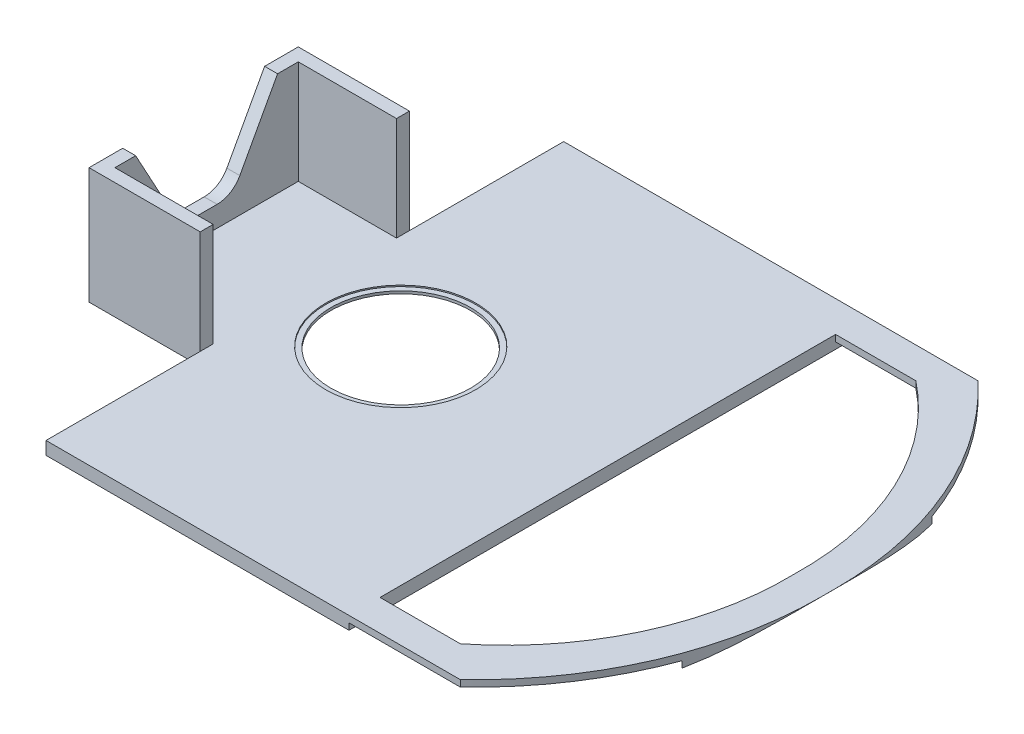
SolidWorks part; units mm, degrees
ref_plane "Front Plane" through (0, 0, 0) normal (0, 0, 1) x (1, 0, 0)
ref_plane "Top Plane" through (0, 0, 0) normal (0, 1, 0) x (1, 0, 0)
ref_plane "Right Plane" through (0, 0, 0) normal (1, 0, 0) x (0, 0, -1)
sketch "Sketch1" plane through (0, 0, 0) normal (0, 1, 0) x (1, 0, 0)
  line L0 (0, 0) -> (203.0139, 0)
  line L1 (0, 100) -> (245, 100) construction
  line L2 (0, 200) -> (0, 0)
  line L3 (191.0139, 12) -> (160, 12)
  line L4 (160, 12) -> (160, 188)
  line L5 (191.0139, 188) -> (160, 188)
  line L6 (0, 200) -> (203.0139, 200)
  line L7 (245, 0) -> (245, 209.5631) construction
  line L8 (245, 100) -> (232.199, 100)
  arc A0 (245, 100) -> (203.0139, 0) centre (111.4511, 97.2578) cw
  arc A1 (232.199, 100) -> (191.0139, 12) centre (123.4511, 97.2578) cw
  arc A2 (245, 100) -> (203.0139, 200) centre (111.4511, 102.7422) ccw
  arc A3 (232.199, 100) -> (191.0139, 188) centre (123.4511, 102.7422) ccw
  point P13 (160, 100)
  dimension "D5" = 12
  dimension "D6" = 12
  dimension "D1" = 200
  dimension "D2" = 12
  dimension "D3" = 160
  dimension "D4" = 245
extrude "Boss-Extrude1" add sketch "Sketch1" along normal blind 5 contours A3 A2 L6 L2 L0 A0 A1 L3 L4 L5 region at (94.4936, 0, -100)
sketch "Sketch6" plane through (0, 5, 0) normal (0, 1, 0) x (1, 0, 0)
  line L0 (0, 100) -> (160, 100) construction
  line L1 (0, 200) -> (0, 0) construction
  line L2 (160, 12) -> (160, 188) construction
  line L3 (42.952, 200) -> (42.952, 140.4135)
  line L4 (0, 0) -> (42.952, 0)
  line L5 (0, 0) -> (0, 59.5865)
  line L6 (0, 59.5865) -> (42.952, 59.5865)
  line L7 (42.952, 0) -> (42.952, 59.5865)
  line L8 (0, 140.4135) -> (42.952, 140.4135)
  line L9 (0, 200) -> (0, 140.4135)
  line L10 (0, 200) -> (42.952, 200)
  circle A0 centre (80, 100) radius 27
  dimension "D1" = 54
extrude "Cut-Extrude4" cut sketch "Sketch6" against normal through all contours A0
sketch "Sketch4" plane through (0, 0, 0) normal (0, 0, 1) x (1, 0, 0)
  line L0 (203.0139, 0) -> (245.0282, 0) construction
  line L1 (160, 2.5) -> (237.0282, 2.5)
  line L2 (160, 2.5) -> (160, 0)
  line L3 (160, 0) -> (237.0282, 0)
  line L4 (237.0282, 2.5) -> (237.0282, 0)
  line L6 (237.0282, 0) -> (245.0282, 0)
  line L7 (245.0282, 0) -> (245.0282, 5)
  arc A0 (237.0282, 0) -> (245.0282, 5) centre (228.901, 21.9035) ccw
  line M1 (0, 0) -> (203.0139, 0)
  line M2 (203.0139, 0) -> (203.0139, 5)
  dimension "D1" = 2.5
  dimension "D2" = 5
  dimension "D3" = 8
extrude "Cut-Extrude2" cut sketch "Sketch4" against normal through all contours L1 L2 M1 M2 | L4 L1 L3 M2 | A0 L6 L7 region at (242.5815, 1.5469, 0) region at (181.507, 1.25, 0) region at (220.021, 1.25, 0)
sketch "Sketch7" plane through (0, 5, 0) normal (0, 1, 0) x (1, 0, 0)
  circle A0 centre (80, 100) radius 29
  dimension "D1" = 58
extrude "Cut-Extrude5" cut sketch "Sketch7" against normal blind 0.5
extrude "Cut-Extrude6" cut sketch "Sketch6<4>" against normal through all
sketch "Sketch6<4>" plane through (0, 5, 0) normal (0, 1, 0) x (1, 0, 0) same geometry as "Sketch6"
sketch "Sketch8" plane through (0, 0, 0) normal (0, -1, 0) x (1, 0, 0)
  line L0 (0, -100) -> (160, -100) construction
  line L1 (0, -140.4135) -> (0, -59.5865) construction
  line L2 (160, 0) -> (160, -200) construction
  line L47 (52.952, -69.5865) -> (10, -69.5865)
  line L48 (52.952, -10) -> (52.952, -69.5865)
  line L49 (150, -10) -> (52.952, -10)
  line L50 (150, -190) -> (150, -10)
  line L51 (52.952, -190) -> (150, -190)
  line L52 (52.952, -130.4135) -> (52.952, -190)
  line L53 (10, -130.4135) -> (52.952, -130.4135)
  line L54 (10, -69.5865) -> (10, -130.4135)
  line L55 (52.952, -69.5865) -> (20, -69.5865)
  line L56 (52.952, -20) -> (52.952, -69.5865)
  line L57 (140, -10) -> (62.952, -10)
  line L58 (150, -180) -> (150, -20)
  line L59 (62.952, -190) -> (140, -190)
  line L60 (52.952, -130.4135) -> (52.952, -180)
  line L61 (20, -130.4135) -> (52.952, -130.4135)
  line L62 (10, -79.5865) -> (10, -120.4135)
  arc A0 (52.952, -20) -> (62.952, -10) centre (62.952, -20) cw
  arc A1 (140, -10) -> (150, -20) centre (140, -20) cw
  arc A2 (150, -180) -> (140, -190) centre (140, -180) cw
  arc A3 (62.952, -190) -> (52.952, -180) centre (62.952, -180) cw
  arc A4 (20, -69.5865) -> (10, -79.5865) centre (20, -79.5865) ccw
  arc A5 (20, -130.4135) -> (10, -120.4135) centre (20, -120.4135) cw
  dimension "D2" = 10
  dimension "D1" = 10
extrude "Cut-Extrude7" cut sketch "Sketch8" against normal offset from surface (3.5 mm away) 1.5 up to face at (121.1832, 5, -100)
sketch "Sketch9" plane through (0, 5, 0) normal (0, 1, 0) x (1, 0, 0)
  line L6 (42.952, 135.4135) -> (42.952, 140.4135)
  line L7 (42.952, 64.5865) -> (42.952, 59.5865)
  line L9 (42.952, 64.5865) -> (5, 64.5865)
  line L10 (5, 64.5865) -> (5, 135.4135)
  line L11 (5, 135.4135) -> (42.952, 135.4135)
  line L12 (42.952, 64.5865) -> (5, 64.5865)
  line L13 (5, 64.5865) -> (5, 135.4135)
  line L14 (5, 135.4135) -> (42.952, 135.4135)
  line L22 (42.952, 200) -> (42.952, 140.4135)
  line L23 (42.952, 140.4135) -> (0, 140.4135)
  line L24 (0, 140.4135) -> (0, 59.5865)
  line L25 (0, 59.5865) -> (42.952, 59.5865)
  line L26 (42.952, 59.5865) -> (42.952, 0)
  line L27 (42.952, 0) -> (203.0139, 0)
  line L28 (203.0139, 200) -> (42.952, 200)
  line L30 (42.952, 140.4135) -> (0, 140.4135)
  line L31 (0, 140.4135) -> (0, 59.5865)
  line L32 (0, 59.5865) -> (42.952, 59.5865)
  arc A4 (203.0139, 0) -> (245.0282, 97.2578) centre (111.4511, 97.2578) ccw
  arc A5 (245.0282, 97.2578) -> (245, 100) centre (111.4511, 97.2578) ccw
  arc A6 (245, 100) -> (245.0282, 102.7422) centre (111.4511, 102.7422) ccw
  arc A7 (245.0282, 102.7422) -> (203.0139, 200) centre (111.4511, 102.7422) ccw
  dimension "D1" = 5
  dimension "D2" = 0
extrude "Boss-Extrude2" add sketch "Sketch9" along normal blind 40
sketch "Sketch10" plane through (5, 0, 0) normal (1, 0, 0) x (0, 0, -1)
  line L0 (100, 45) -> (100, -3.5923) construction
  line L1 (64.5865, 45) -> (135.4135, 45) construction
  line L2 (64.5865, 45) -> (72.5865, 45) construction
  line L3 (72.5865, 45) -> (87.1593, 18.2202)
  line L4 (104.057, 13) -> (95.943, 13)
  line L5 (97.2578, 5) -> (0, 5) construction
  line L6 (72.5865, 45) -> (127.4135, 45)
  line L7 (127.4135, 45) -> (112.8407, 18.2202)
  arc A0 (95.943, 13) -> (87.1593, 18.2202) centre (95.943, 23) cw
  arc A1 (104.057, 13) -> (112.8407, 18.2202) centre (104.057, 23) ccw
  point P13 (90, 13)
  point P15 (100, 13)
  dimension "D4" = 10
  dimension "D1" = 8
  dimension "D2" = 8
  dimension "D3" = 10
extrude "Cut-Extrude9" cut sketch "Sketch10" against normal blind 40
